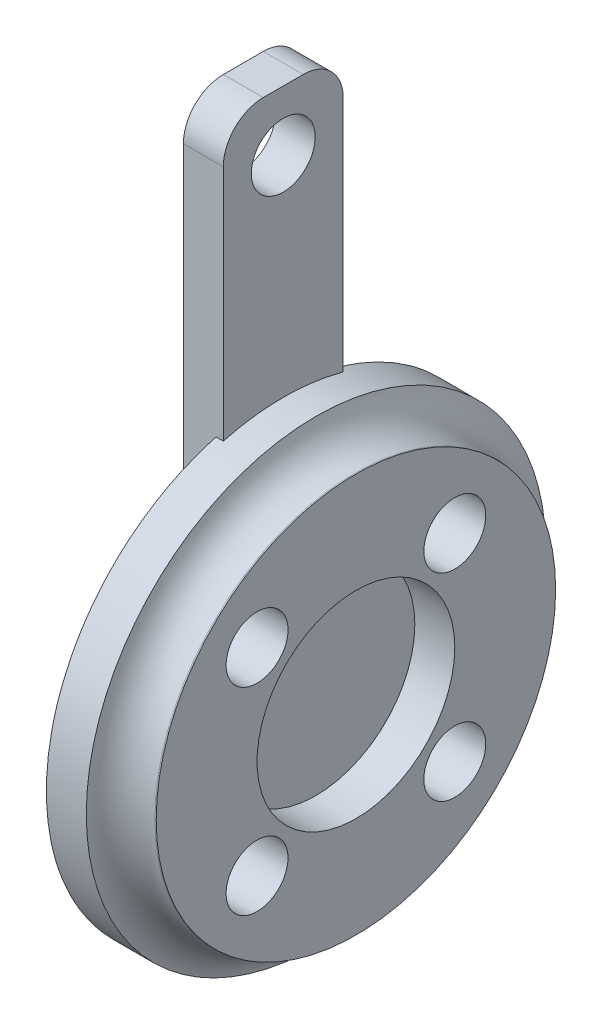
SolidWorks part; units mm, degrees
material "PLA"
ref_plane "Front Plane" through (0, 0, 0) normal (1, 0, 0) x (0, 1, 0)
ref_plane "Top Plane" through (0, 0, 0) normal (0, 0, 1) x (0, 1, 0)
ref_plane "Right Plane" through (0, 0, 0) normal (0, 1, 0) x (-1, 0, 0)
sketch "Sketch1" plane through (0, 0, 0) normal (1, 0, 0) x (0, 1, 0)
  circle A0 centre (0, 0) radius 11.5
  circle A1 centre (0, 0) radius 10.5
  dimension "D1" = 1
  dimension "D2" = 21
extrude "Boss-Extrude1" add sketch "Sketch1" along normal blind 2
extrude "Boss-Extrude2" add sketch "Sketch1<2>" along normal up to surface (2 mm away) contours A1 region at (0, 0, 0) up to face at (2, 0, -11.5)
sketch "Sketch1<2>" plane through (0, 0, 0) normal (1, 0, 0) x (0, 1, 0) same geometry as "Sketch1"
ref_plane "Plane1" through (-1.64, 0, 0) normal (-1, 0, 0) x (0, 0, 1)
sketch "Sketch2" plane through (-1.64, 0, 0) normal (-1, 0, 0) x (0, 0, 1)
  line L1 (-3, -5) -> (3, -5)
  line L2 (-3, -5) -> (-3, 5)
  line L3 (-3, 5) -> (3, 5)
  line L4 (3, -5) -> (3, 5)
  line L5 (0, 5) -> (0, -5) construction
  line L6 (-3, 0) -> (3, 0) construction
  point P0 (0, 0)
  dimension "D1" = 6
  dimension "D2" = 10
sketch "Sketch3" plane through (0, 0, 0) normal (-1, 0, 0) x (0, -1, 0)
  circle A0 centre (0, 0) radius 11.5
  circle A1 centre (0, 0) radius 9.5
  circle A2 centre (0, 0) radius 11.5 construction
  dimension "D1" = 2
extrude "Cut-Extrude2" cut sketch "Sketch3" against normal blind 1.5 contours A1 region at (0, 0, 0)
sketch "Sketch4" plane through (0, 0, 0) normal (-1, 0, 0) x (0, -1, 0)
  circle A1 centre (0, 0) radius 11.5
  circle A2 centre (0, 0) radius 11.5
  dimension "D1" = 0
loft "Loft1" add profiles "Sketch4", "Sketch2" connector at (0, 0, 11.5) connector at (-1.64, -5, -3)
sketch "Sketch6" plane through (-1.64, 0, 0) normal (-1, 0, 0) x (0, -1, 0)
  line L0 (0, 0) -> (-22, 0) construction
  line L1 (5, 3) -> (-25, 3)
  line L2 (-25, 3) -> (-25, -3)
  line L3 (-25, -3) -> (5, -3)
  line L4 (5, -3) -> (5, 3)
  circle A1 centre (-22, 0) radius 1.6
  dimension "D2" = 3.2
  dimension "D1" = 22
  dimension "D3" = 3
extrude "Boss-Extrude3" add sketch "Sketch6" against normal blind 2
sketch "Sketch7" plane through (2, 0, 0) normal (1, 0, 0) x (0, 1, 0)
  line L0 (0, 25.0823) -> (0, -32.3177) construction
  line L1 (-4.95, 4.95) -> (4.95, 4.95) construction
  line L2 (15.5615, 0) -> (-15.5615, 0) construction
  line L3 (4.95, 4.95) -> (4.95, -4.95) construction
  line L4 (-4.95, 4.95) -> (-4.95, -4.95) construction
  line L5 (-4.95, -4.95) -> (4.95, -4.95) construction
  circle A0 centre (0, 0) radius 10
  circle A1 centre (-4.95, 4.95) radius 1
  circle A2 centre (4.95, 4.95) radius 1
  circle A3 centre (4.95, -4.95) radius 1
  circle A4 centre (-4.95, -4.95) radius 1
  circle A5 centre (0, 0) radius 4.95
  dimension "D1" = 20
  dimension "D2" = 2
  dimension "D3" = 9.9
extrude "Boss-Extrude4" add sketch "Sketch7" along normal blind 2
fillet "Fillet1" radius 2 1 edges at (2, 0, -10)
fillet "Fillet2" radius 2 2 edges at (-0.64, 25, 3) (-0.64, 25, -3)
sketch "Sketch8" plane through (4, 0, 0) normal (1, 0, 0) x (0, 1, 0)
  circle A0 centre (-4.95, -4.95) radius 1 construction
  circle A1 centre (4.95, -4.95) radius 1 construction
  circle A2 centre (4.95, 4.95) radius 1 construction
  circle A3 centre (-4.95, 4.95) radius 1 construction
  circle A4 centre (-4.95, -4.95) radius 1
  circle A5 centre (4.95, -4.95) radius 1
  circle A6 centre (4.95, 4.95) radius 1
  circle A7 centre (-4.95, 4.95) radius 1
  circle A8 centre (4.95, 4.95) radius 1.55
  circle A9 centre (-4.95, 4.95) radius 1.55
  circle A10 centre (-4.95, -4.95) radius 1.55
  circle A11 centre (4.95, -4.95) radius 1.55
  circle A12 centre (-4.95, 4.95) radius 2.55
  circle A13 centre (4.95, 4.95) radius 2.55
  circle A14 centre (-4.95, -4.95) radius 2.55
  circle A15 centre (4.95, -4.95) radius 2.55
  circle M1 centre (-4.95, -4.95) radius 1
  circle M2 centre (4.95, 4.95) radius 1
  circle M4 centre (-4.95, 4.95) radius 1
  circle M5 centre (4.95, -4.95) radius 1
  dimension "D1" = 3.1
  dimension "D2" = 1
extrude "Cut-Extrude3" cut sketch "Sketch8" against normal through all both and the other way through all contours A9 M4 | A8 M2 | M2 | M4 | M1 | A10 M1 | M5 | A11 M5 region at (4, -4.95, -4.95) region at (4, 4.95, -4.95) region at (4, 4.95, 4.95) region at (4, -4.95, 4.95) region at (4, 3.4438, 4.95) region at (4, -6.4562, 4.95) region at (4, -6.4562, -4.95) region at (4, 3.4438, -4.95)
sketch "Sketch9" plane through (1.5, 0, 0) normal (-1, 0, 0) x (0, -1, 0)
  circle A1 centre (0, 0) radius 9.5
  circle A2 centre (0, 0) radius 9.5
  circle M2 centre (-4.95, -4.95) radius 1.55
  circle M3 centre (4.95, -4.95) radius 1.55
  circle M4 centre (4.95, 4.95) radius 1.55
  circle M5 centre (-4.95, 4.95) radius 1.55
  circle M6 centre (0, 0) radius 9.5
  dimension "D1" = 0
extrude "Boss-Extrude5" add sketch "Sketch9" along normal up to surface (1.5 mm away) contours M6 M3 M5 M4 M2 region at (1.5, 0, 0) up to face at (0, 4.95, -3.4)
extrude "Cut-Extrude4" cut sketch "Sketch8<3>" along normal offset from surface 3 and the other way through all from surface contours A15 | A13 | A12 | A14 up to face at (4, 4.95, -6.5) starting at face at (-1.64, 12.1036, -0.375)
sketch "Sketch8<3>" plane through (4, 0, 0) normal (1, 0, 0) x (0, 1, 0) same geometry as "Sketch8"
fillet "Fillet3" radius 10 2 edges at (-1.4024, 6.5932, -3) (-1.4024, 6.5932, 3)
